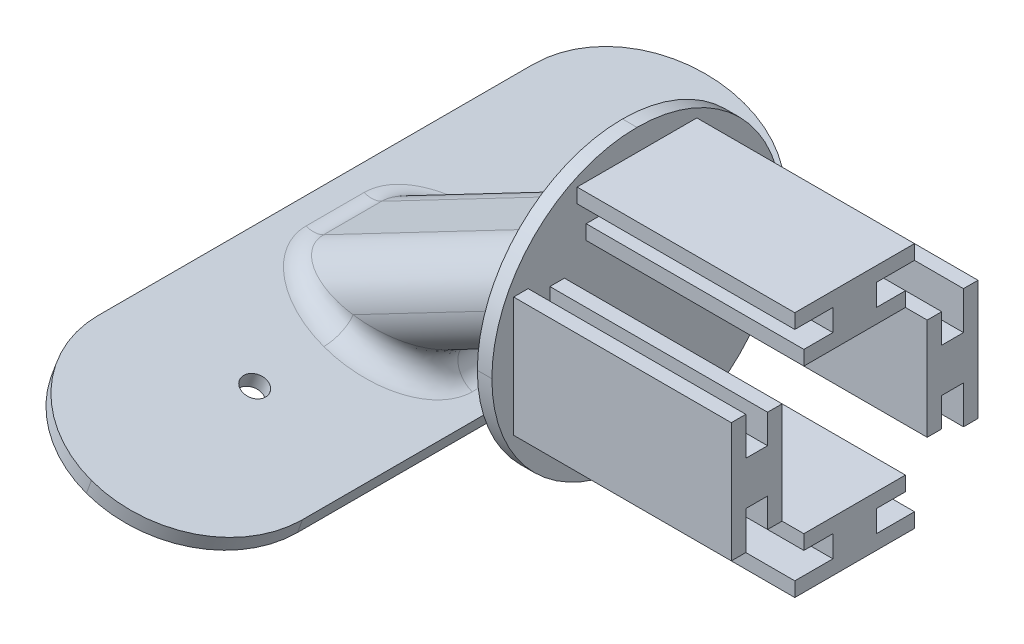
SolidWorks part; units mm, degrees
ref_plane "Front Plane" through (0, 0, 0) normal (0, 0, 1) x (1, 0, 0)
ref_plane "Top Plane" through (0, 0, 0) normal (0, 1, 0) x (1, 0, 0)
ref_plane "Right Plane" through (0, 0, 0) normal (1, 0, 0) x (0, 0, -1)
sketch "Sketch1" plane through (0, 0, 0) normal (0, 0, 1) x (1, 0, 0)
  line L0 (0, -20) -> (0, 20)
  line L1 (0, -20) -> (0, -25) construction
  line L2 (0, -25) -> (-14.0954, -19.8697) construction
  line L3 (-14.0954, -19.8697) -> (-42.2862, -9.6091)
  line L4 (-42.2862, -9.6091) -> (-42.9702, -11.4885)
  line L5 (-42.9702, -11.4885) -> (-14.7794, -21.7491)
  line L6 (-14.7794, -21.7491) -> (-14.0954, -19.8697)
  line L7 (0, 20) -> (2, 20)
  line L8 (2, 20) -> (2, -20)
  line L9 (0, -20) -> (2, -20)
  line L10 (-28.1908, -14.7394) -> (0, 0)
  line L11 (-38.3704, -11.0343) -> (0, 9.0275)
  line L12 (-26.3374, -18.2841) -> (-25.5009, -17.8468)
  line L13 (-23.1009, -16.5919) -> (0, -4.5137)
  line L14 (-38.3704, -11.0343) -> (-28.1908, -14.7394)
  line L15 (-26.3374, -18.2841) -> (1.8533, -3.5447) construction
  line L16 (-28.1908, -14.7394) -> (-23.1009, -16.5919)
  line L17 (0, 9.0275) -> (0, 0)
  line L18 (0, -4.5137) -> (0, 0)
  point P4 (0, 0)
  dimension "D1" = 40
  dimension "D2" = 5
  dimension "D3" = 70
  dimension "D4" = 15
  dimension "D5" = 30
  dimension "D6" = 2
  dimension "D7" = 2
  dimension "D8" = 8
  dimension "D9" = 4
extrude "Boss-Extrude1" add sketch "Sketch1" along normal mid plane 90 contours L5 L6 L3 L4 region at (-28.5328, -15.6791, 0)
extrude "Boss-Extrude2" add sketch "Sketch1<3>" along normal mid plane 40 separate body contours L0 L7 L8 L9
sketch "Sketch1<3>" plane through (0, 0, 0) normal (0, 0, 1) x (1, 0, 0) same geometry as "Sketch1"
extrude "Boss-Extrude3" add sketch "Sketch1<4>" along normal mid plane 20 contours L11 L3 L10 L0 | L3 L13 L0 L10 region at (-12.865, -8.9086, 0) region at (-16.77, -4.0243, 0)
sketch "Sketch1<4>" plane through (0, 0, 0) normal (0, 0, 1) x (1, 0, 0) same geometry as "Sketch1"
sketch "Sketch2" plane through (2, 0, 0) normal (1, 0, 0) x (0, 0, -1)
  line L0 (0, 0) -> (0, 20) construction
  line L1 (-20, 20) -> (20, 20) construction
  line L2 (0, 0) -> (0, 15) construction
  line L3 (-15, -15) -> (15, -15) construction
  line L4 (-15, -15) -> (-15, 15) construction
  line L5 (-15, 15) -> (15, 15) construction
  line L6 (15, -15) -> (15, 15) construction
  line L7 (-15, -15) -> (15, 15) construction
  line L8 (-15, 15) -> (15, -15) construction
  line L9 (-8.25, 15) -> (8.25, 15)
  line L10 (-8.25, 15) -> (-8.25, 17)
  line L11 (-8.25, 17) -> (8.25, 17)
  line L12 (8.25, 17) -> (8.25, 15)
  line L13 (-7, 12) -> (7, 12)
  line L14 (-7, 12) -> (-7, 10)
  line L15 (-7, 10) -> (7, 10)
  line L16 (7, 10) -> (7, 12)
  line L17 (-3, 15) -> (-3, 12)
  line L18 (3, 15) -> (3, 12)
  line L19 (15, 8.25) -> (15, -8.25)
  line L20 (17, -8.25) -> (15, -8.25)
  line L21 (17, 8.25) -> (17, -8.25)
  line L22 (15, 8.25) -> (17, 8.25)
  line L23 (12, 7) -> (12, -7)
  line L24 (10, -7) -> (12, -7)
  line L25 (10, 7) -> (10, -7)
  line L26 (12, 7) -> (10, 7)
  line L27 (15, -3) -> (12, -3)
  line L28 (15, 3) -> (12, 3)
  line L29 (8.25, -15) -> (-8.25, -15)
  line L30 (-8.25, -17) -> (-8.25, -15)
  line L31 (8.25, -17) -> (-8.25, -17)
  line L32 (8.25, -15) -> (8.25, -17)
  line L33 (7, -12) -> (-7, -12)
  line L34 (-7, -10) -> (-7, -12)
  line L35 (7, -10) -> (-7, -10)
  line L36 (7, -12) -> (7, -10)
  line L37 (-3, -15) -> (-3, -12)
  line L38 (3, -15) -> (3, -12)
  line L39 (-15, -8.25) -> (-15, 8.25)
  line L40 (-17, 8.25) -> (-15, 8.25)
  line L41 (-17, -8.25) -> (-17, 8.25)
  line L42 (-15, -8.25) -> (-17, -8.25)
  line L43 (-12, -7) -> (-12, 7)
  line L44 (-10, 7) -> (-12, 7)
  line L45 (-10, -7) -> (-10, 7)
  line L46 (-12, -7) -> (-10, -7)
  line L47 (-15, 3) -> (-12, 3)
  line L48 (-15, -3) -> (-12, -3)
  point P5 (0, 0)
  point P15 (0, 15)
  point P20 (0, 12)
  point P65 (0, 0)
  dimension "D1" = 30
  dimension "D2" = 30
  dimension "D3" = 16.5
  dimension "D4" = 2
  dimension "D5" = 3
  dimension "D6" = 14
  dimension "D7" = 2
  dimension "D8" = 3
  dimension "D9" = 4
extrude "Boss-Extrude4" add sketch "Sketch2" along normal blind 30 contours L23 L26 L25 L24 | L19 L28 L23 L27 | L18 L9 L17 L13 | L12 L11 L10 L9 | L43 L46 L45 L44 | L39 L48 L43 L47 | L42 L39 L40 L41 | L33 L36 L35 L34 | L29 L38 L33 L37 | L32 L29 L30 L31 | L21 L20 L19 L22 | L13 L16 L15 L14 region at (2, 16, 0) region at (2, 13.5, 0) region at (2, 0, -13.5) region at (2, 0, -11) region at (2, -16, 0) region at (2, -13.5, 0) region at (2, -11, 0) region at (2, 0, 16) region at (2, 0, 13.5) region at (2, 0, 11)
sketch "Sketch3" plane through (-8.7189, -23.9549, 0) normal (-0.342, -0.9397, 0) x (0.9397, -0.342, 0)
  line L0 (-6.4495, 0) -> (-36.4495, 0) construction
  line L1 (-6.4495, 45) -> (-6.4495, -45) construction
  line L2 (-36.4495, 45) -> (-36.4495, -45) construction
  line L3 (-21.4495, 0) -> (-21.4495, 22.5) construction
  circle A0 centre (-21.4495, 22.5) radius 1.6
  circle A1 centre (-21.4495, -22.5) radius 1.6
  dimension "D2" = 3.2
  dimension "D1" = 22.5
extrude "Cut-Extrude1" cut sketch "Sketch3" against normal through all
fillet "Fillet1" radius 20 4 edges at (1, -20, -20) (1, -20, 20) (1, 20, -20) (1, 20, 20)
fillet "Fillet2" radius 15 4 edges at (-14.4374, -20.8094, -45) (-42.6282, -10.5488, -45) (-14.4374, -20.8094, 45) (-42.6282, -10.5488, 45)
fillet "Fillet3" radius 6 4 edges at (-11.5505, -10.5528, -10) (-11.5505, -10.5528, 10) (-19.1852, -1.0034, 10) (-19.1852, -1.0034, -10)
fillet "Fillet4" radius 5 6 edges at (0, 7.0444, 8.2426) (0, -2.5307, 8.2426) (0, -4.5137, 0) (0, -2.5307, -8.2426) (0, 7.0444, -8.2426) (0, 9.0275, 0)
fillet "Fillet5" radius 3 6 edges at (-25.3371, -15.778, 8.2426) (-23.1009, -16.5919, 0) (-25.3371, -15.778, -8.2426) (-36.1343, -11.8482, -8.2426) (-38.3704, -11.0343, 0) (-36.1343, -11.8482, 8.2426)
